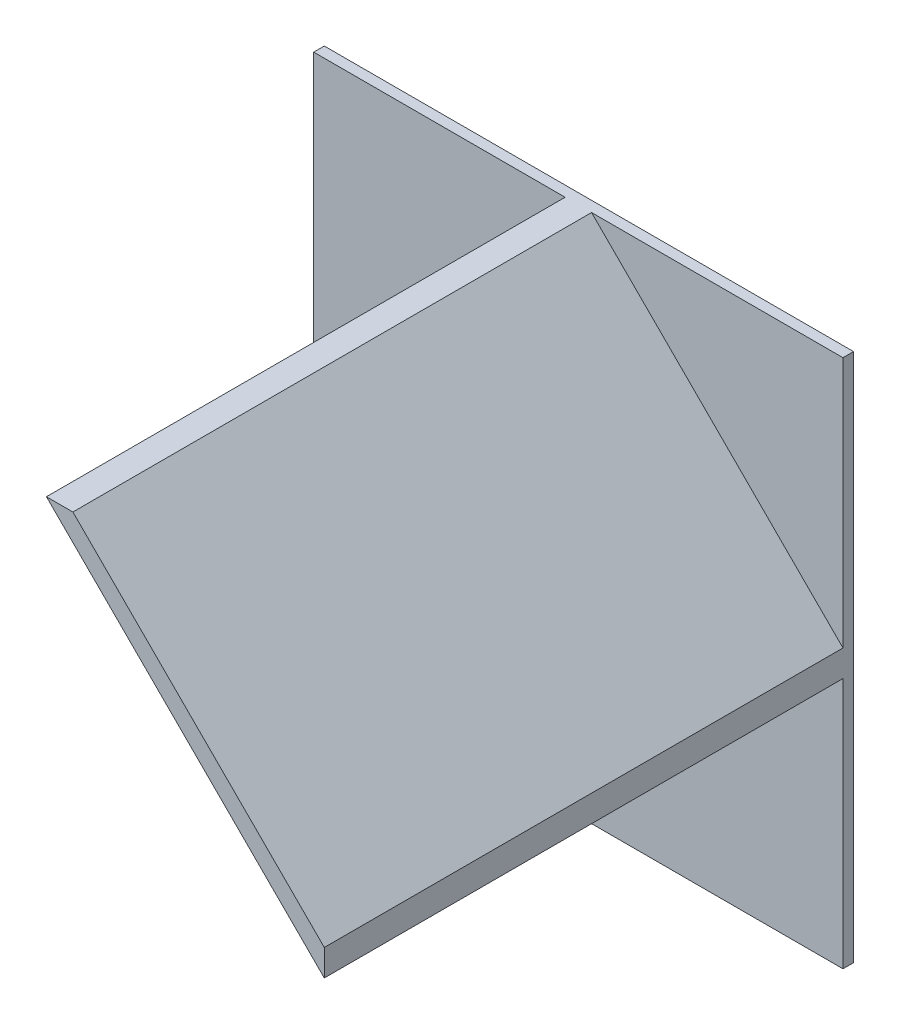
SolidWorks part; units mm, degrees
ref_plane "Płaszczyzna przednia" through (0, 0, 0) normal (0, 0, 1) x (1, 0, 0)
ref_plane "Płaszczyzna górna" through (0, 0, 0) normal (0, 1, 0) x (1, 0, 0)
ref_plane "Płaszczyzna prawa" through (0, 0, 0) normal (1, 0, 0) x (0, 0, -1)
sketch "Szkic1" plane through (0, 0, 0) normal (0, 0, 1) x (1, 0, 0)
  line L0 (0, 0) -> (100, 0)
  line L1 (0, 0) -> (-100, 0)
  line L2 (0, 0) -> (0, 100)
  line L3 (0, 0) -> (0, -100)
  line L4 (0, 100) -> (100, 100)
  line L5 (100, 100) -> (100, 0)
  line L6 (100, -100) -> (0, -100)
  line L7 (100, 0) -> (100, -100)
  line L8 (0, 100) -> (-100, 100)
  line L9 (-100, 100) -> (-100, 0)
  line L10 (-100, -100) -> (-100, 0)
  line L11 (0, -100) -> (-100, -100)
  dimension "D1" = 100
  dimension "D2" = 100
  dimension "D3" = 100
  dimension "D4" = 100
  dimension "D5" = 100
  dimension "D6" = 100
  dimension "D7" = 100
  dimension "D8" = 100
  dimension "D9" = 100
  dimension "D10" = 100
  dimension "D11" = 100
extrude "Dodanie-wyciągnięcie1" add sketch "Szkic1" along normal blind 4 contours L8 L9 L1 L2 | L5 L4 L2 L0 | L7 L0 L3 L6 | L11 L3 L1 L10 region at (50, 50, 0) region at (-50, -50, 0) region at (-50, 50, 0) region at (50, -50, 0)
sketch "Szkic2" plane through (0, 0, 4) normal (0, 0, 1) x (1, 0, 0)
  line L1 (100, 100) -> (-100, 100) construction
  line L2 (100, -100) -> (-100, -100) construction
  line L9 (-2, -100) -> (2, -100)
  line L24 (0, 100) -> (5, 100)
  line L25 (0, 100) -> (-5, 100)
  line L26 (100, 0) -> (100, 5)
  line L27 (100, 100) -> (100, -100) construction
  line L28 (100, 0) -> (100, -5)
  line L29 (5, 100) -> (100, 5)
  line L30 (-5, 100) -> (100, -5)
  dimension "D1" = 5
  dimension "D2" = 5
  dimension "D3" = 5
  dimension "D4" = 5
  dimension "D8" = 4
extrude "Dodanie-wyciągnięcie4" add sketch "Szkic2" along normal blind 196 contours L28 L30 L25 L24 L29 L26
